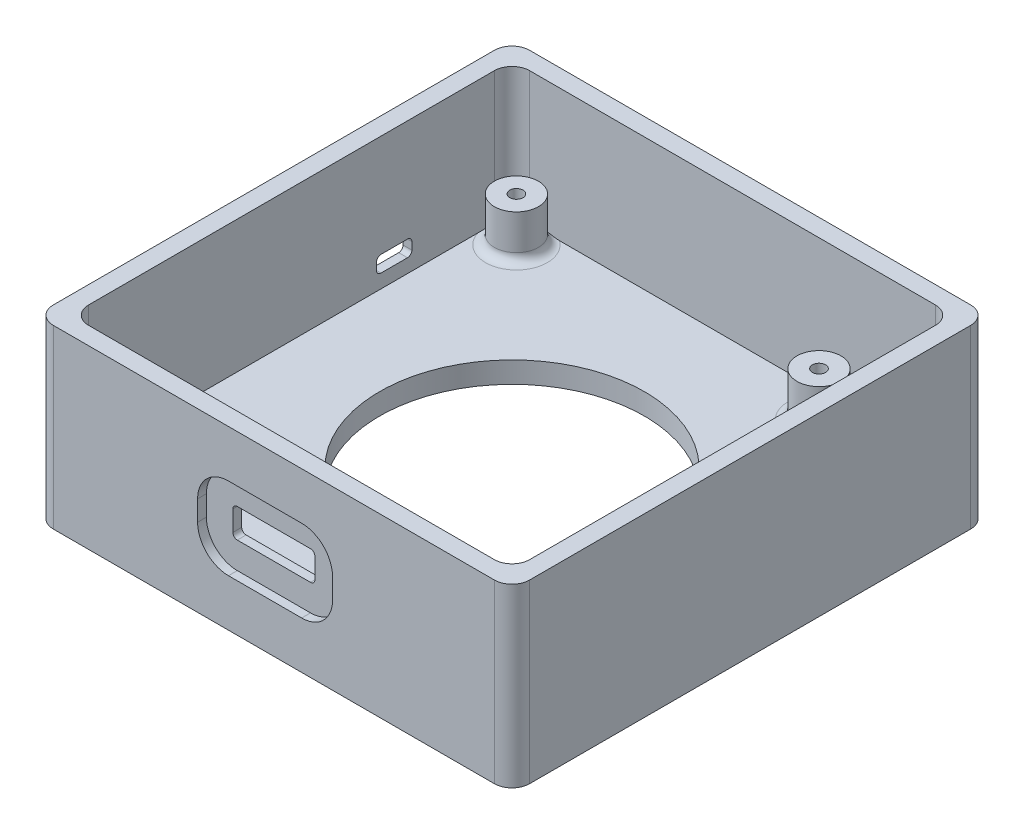
SolidWorks part; units mm, degrees
ref_plane "前视基准面" through (0, 0, 0) normal (0, 0, 1) x (1, 0, 0)
ref_plane "上视基准面" through (0, 0, 0) normal (0, 1, 0) x (1, 0, 0)
ref_plane "右视基准面" through (0, 0, 0) normal (1, 0, 0) x (0, 0, -1)
sketch "草图1" plane through (0, 0, 0) normal (0, 1, 0) x (1, 0, 0)
  line L1 (27, 27) -> (-27, 27)
  line L2 (27, 27) -> (27, -27)
  line L3 (27, -27) -> (-27, -27)
  line L4 (-27, 27) -> (-27, -27)
  line L5 (27, 27) -> (-27, -27) construction
  line L6 (27, -27) -> (-27, 27) construction
  point P1 (0, 0)
extrude "凸台-拉伸1" add sketch "草图1" along normal blind 20
sketch "草图2" plane through (0, 20, 0) normal (0, 1, 0) x (1, 0, 0)
  line L0 (-25, 25) -> (-25, -25)
  line L1 (-25, -25) -> (25, -25)
  line L2 (25, -25) -> (25, 25)
  line L3 (25, 25) -> (-25, 25)
  line L4 (-27, 27) -> (-27, -27)
  line L5 (-27, -27) -> (27, -27)
  line L6 (27, -27) -> (27, 27)
  line L7 (27, 27) -> (-27, 27)
  line L8 (-27, 27) -> (-27, -27)
  line L9 (-27, -27) -> (27, -27)
  line L10 (27, -27) -> (27, 27)
  line L11 (27, 27) -> (-27, 27)
  dimension "D1" = 0
  dimension "D2" = 2
extrude "切除-拉伸1" cut sketch "草图2" against normal blind 15 contours L2 L3 L0 L1 region at (0, 20, 0)
sketch "草图3" plane through (0, 5, 0) normal (0, 1, 0) x (1, 0, 0)
  line L0 (-25, 25) -> (-25, -25) construction
  circle A0 centre (-21.65, 22.15) radius 2.5
  circle A1 centre (-21.65, -22.15) radius 2.5
  circle A2 centre (-21.65, -22.15) radius 0.75
  circle A3 centre (-21.65, 22.15) radius 0.75
  dimension "D1" = 5
  dimension "D2" = 5
  dimension "D4" = 22.15
  dimension "D7" = 21.65
  dimension "D3" = 44.3
  dimension "D5" = 3.35
  dimension "D6" = 0
extrude "凸台-拉伸2" add sketch "草图3" along normal blind 5
fillet "圆角1" radius 1 2 edges at (-21.65, 5, 24.65) (-21.65, 5, -19.65)
ref_plane "基准面6" through (-4.5, 0, 0) normal (1, 0, 0) x (0, 0, -1)
mirror "镜向2" about plane through (-4.5, 0, 0) normal (1, 0, 0) of "圆角1", "凸台-拉伸2"
sketch "草图4" plane through (0, 0, 0) normal (0, -1, 0) x (-1, 0, 0)
  circle A0 centre (0, 0) radius 21.9
extrude "切除-拉伸2" cut sketch "草图4" against normal blind 1 contours A0
sketch "草图6" plane through (0, 1, 0) normal (0, -1, 0) x (1, 0, 0)
  circle A0 centre (0, 0) radius 18.5
extrude "切除-拉伸4" cut sketch "草图6" against normal blind 1.6
sketch "草图8" plane through (0, 2.6, 0) normal (0, -1, 0) x (1, 0, 0)
  circle A0 centre (0, 0) radius 15
extrude "切除-拉伸5" cut sketch "草图8" against normal blind 5
sketch "草图9" plane through (0, 5, 0) normal (0, 1, 0) x (1, 0, 0)
  line L1 (-3.1528, 8.925) -> (21.0647, 8.925)
  line L2 (-3.1528, 8.925) -> (-3.1528, -8.925)
  line L3 (-3.1528, -8.925) -> (21.0647, -8.925)
  line L4 (21.0647, 8.925) -> (21.0647, -8.925)
  line L5 (8.9559, -8.925) -> (8.9559, 8.925) construction
  line L6 (-3.1528, 0) -> (21.0647, 0) construction
  point P0 (8.9559, 0)
  dimension "D1" = 17.85
sketch "草图10" plane through (0, 0, 0) normal (0, -1, 0) x (1, 0, 0)
  line L0 (19.9989, -8.925) -> (-3.1528, -8.925)
  line L1 (19.9989, -8.925) -> (19.9989, 8.925)
  line L2 (-3.1528, -8.925) -> (-3.1528, 8.925)
  line L3 (-3.1528, 8.925) -> (19.9989, 8.925)
  line L4 (-27, 27) -> (-27, -27)
  line L5 (-27, -27) -> (27, -27)
  line L6 (27, -27) -> (27, 27)
  line L7 (27, 27) -> (-27, 27)
  line L8 (-27, 27) -> (-27, -27)
  line L9 (-27, -27) -> (27, -27)
  line L10 (27, -27) -> (27, 27)
  line L11 (27, 27) -> (-27, 27)
  circle A0 centre (0, 0) radius 21.9 construction
  circle A1 centre (0, 0) radius 21.9
  circle M8 centre (0, 0) radius 21.9
  dimension "D2" = 17.85
  dimension "D1" = 0
extrude "切除-拉伸6" cut sketch "草图10" against normal blind 10 contours L1 M8 | L3 L2 L0 L1 region at (8.423, 0, 0) region at (20.7622, 0, 0)
sketch "草图11" plane through (0, 0, 27) normal (0, 0, 1) x (1, 0, 0)
  line L0 (12.65, 10) -> (-0.99, 10)
  line L1 (13.4, 10) -> (11.9, 10) construction
  line L2 (-5.14, 14.65) -> (3.16, 14.65)
  line L3 (-5.14, 11.65) -> (3.16, 11.65)
  line L4 (-5.64, 11.15) -> (-5.64, 8.85)
  line L5 (-5.14, 8.35) -> (3.16, 8.35)
  line L6 (3.66, 11.15) -> (3.66, 8.85)
  line L7 (-0.99, 8.35) -> (-0.99, 11.65) construction
  line L8 (-5.64, 10) -> (3.66, 10) construction
  line L9 (6.66, 11.15) -> (6.66, 8.85)
  line L10 (-5.14, 5.35) -> (3.16, 5.35)
  line L11 (-8.64, 11.15) -> (-8.64, 8.85)
  arc A0 (-5.14, 11.65) -> (-5.64, 11.15) centre (-5.14, 11.15) ccw
  arc A1 (-5.64, 8.85) -> (-5.14, 8.35) centre (-5.14, 8.85) ccw
  arc A2 (3.16, 8.35) -> (3.66, 8.85) centre (3.16, 8.85) ccw
  arc A3 (3.16, 11.65) -> (3.66, 11.15) centre (3.16, 11.15) cw
  arc A4 (3.16, 14.65) -> (6.66, 11.15) centre (3.16, 11.15) cw
  arc A5 (3.16, 5.35) -> (6.66, 8.85) centre (3.16, 8.85) ccw
  arc A6 (-8.64, 8.85) -> (-5.14, 5.35) centre (-5.14, 8.85) ccw
  arc A7 (-5.14, 14.65) -> (-8.64, 11.15) centre (-5.14, 11.15) ccw
  point P10 (-5.64, 11.65)
  point P15 (3.66, 8.35)
  point P18 (3.66, 11.65)
  dimension "D3" = 0.5
  dimension "D1" = 9.3
  dimension "D2" = 3.3
  dimension "D4" = 3
extrude "切除-拉伸8" cut sketch "草图11" against normal blind 0.5 contours L2 A7 L11 A6 L10 A5 L9 L6 A2 L5 A1 L4 A0 L3 A3 A4 region at (6.481, 9.425, 27)
sketch "草图13" plane through (0, 0, 27) normal (0, 0, 1) x (1, 0, 0)
  line L0 (-5.14, 11.65) -> (3.16, 11.65) construction
  line L1 (-5.14, 11.65) -> (3.16, 11.65)
  line L6 (3.66, 8.85) -> (3.66, 11.15)
  line L7 (3.16, 11.65) -> (-5.14, 11.65)
  line L8 (-5.64, 11.15) -> (-5.64, 8.85)
  line L9 (-5.14, 8.35) -> (3.16, 8.35)
  line L10 (3.66, 8.85) -> (3.66, 11.15)
  line L11 (3.16, 11.65) -> (-5.14, 11.65)
  line L12 (-5.64, 11.15) -> (-5.64, 8.85)
  line L13 (-5.14, 8.35) -> (3.16, 8.35)
  arc A4 (3.66, 11.15) -> (3.16, 11.65) centre (3.16, 11.15) ccw
  arc A5 (-5.14, 11.65) -> (-5.64, 11.15) centre (-5.14, 11.15) ccw
  arc A6 (-5.64, 8.85) -> (-5.14, 8.35) centre (-5.14, 8.85) ccw
  arc A7 (3.16, 8.35) -> (3.66, 8.85) centre (3.16, 8.85) ccw
  arc A8 (3.66, 11.15) -> (3.16, 11.65) centre (3.16, 11.15) ccw
  arc A9 (-5.14, 11.65) -> (-5.64, 11.15) centre (-5.14, 11.15) ccw
  arc A10 (-5.64, 8.85) -> (-5.14, 8.35) centre (-5.14, 8.85) ccw
  arc A11 (3.16, 8.35) -> (3.66, 8.85) centre (3.16, 8.85) ccw
  line M9 (3.66, 8.85) -> (3.66, 11.15)
  arc M10 (3.66, 11.15) -> (3.16, 11.65) centre (3.16, 11.15) ccw
  line M11 (3.16, 11.65) -> (-5.14, 11.65)
  arc M12 (-5.14, 11.65) -> (-5.64, 11.15) centre (-5.14, 11.15) ccw
  line M13 (-5.64, 11.15) -> (-5.64, 8.85)
  arc M14 (-5.64, 8.85) -> (-5.14, 8.35) centre (-5.14, 8.85) ccw
  line M15 (-5.14, 8.35) -> (3.16, 8.35)
  arc M16 (3.16, 8.35) -> (3.66, 8.85) centre (3.16, 8.85) ccw
  dimension "D1" = 0
extrude "切除-拉伸9" cut sketch "草图13" against normal blind 10 contours M16 M9 M10 M11 M12 M13 M14 M15 region at (-0.99, 10, 27)
sketch "草图14" plane through (-27, 0, 0) normal (-1, 0, 0) x (0, 0, 1)
  line L7 (-10.15, 6.5578) -> (-13.15, 6.5578)
  line L8 (-9.65, 7.8878) -> (-9.65, 7.0578)
  line L9 (-13.65, 7.0578) -> (-13.65, 7.8878)
  line L10 (-13.15, 8.3878) -> (-10.15, 8.3878)
  line L15 (-13.15, 10.3878) -> (-10.15, 10.3878)
  line L16 (-7.65, 7.8878) -> (-7.65, 7.0578)
  line L17 (-10.15, 4.5578) -> (-13.15, 4.5578)
  line L18 (-15.65, 7.0578) -> (-15.65, 7.8878)
  arc A0 (-9.65, 7.0578) -> (-10.15, 6.5578) centre (-10.15, 7.0578) cw
  arc A1 (-10.15, 8.3878) -> (-9.65, 7.8878) centre (-10.15, 7.8878) cw
  arc A2 (-13.65, 7.8878) -> (-13.15, 8.3878) centre (-13.15, 7.8878) cw
  arc A3 (-13.15, 6.5578) -> (-13.65, 7.0578) centre (-13.15, 7.0578) cw
  arc A8 (-15.65, 7.8878) -> (-13.15, 10.3878) centre (-13.15, 7.8878) cw
  arc A9 (-10.15, 10.3878) -> (-7.65, 7.8878) centre (-10.15, 7.8878) cw
  arc A10 (-7.65, 7.0578) -> (-10.15, 4.5578) centre (-10.15, 7.0578) cw
  arc A11 (-13.15, 4.5578) -> (-15.65, 7.0578) centre (-13.15, 7.0578) cw
extrude "切除-拉伸10" cut sketch "草图14" against normal blind 0.5
sketch "草图15" plane through (-27, 0, 0) normal (-1, 0, 0) x (0, 0, 1)
  line L4 (-9.65, 7.0578) -> (-9.65, 7.8878)
  line L5 (-10.15, 8.3878) -> (-13.15, 8.3878)
  line L6 (-13.65, 7.8878) -> (-13.65, 7.0578)
  line L7 (-13.15, 6.5578) -> (-10.15, 6.5578)
  line L8 (-9.65, 7.0578) -> (-9.65, 7.8878)
  line L9 (-10.15, 8.3878) -> (-13.15, 8.3878)
  line L10 (-13.65, 7.8878) -> (-13.65, 7.0578)
  line L11 (-13.15, 6.5578) -> (-10.15, 6.5578)
  arc A4 (-10.15, 6.5578) -> (-9.65, 7.0578) centre (-10.15, 7.0578) ccw
  arc A5 (-9.65, 7.8878) -> (-10.15, 8.3878) centre (-10.15, 7.8878) ccw
  arc A6 (-13.15, 8.3878) -> (-13.65, 7.8878) centre (-13.15, 7.8878) ccw
  arc A7 (-13.65, 7.0578) -> (-13.15, 6.5578) centre (-13.15, 7.0578) ccw
  arc A8 (-10.15, 6.5578) -> (-9.65, 7.0578) centre (-10.15, 7.0578) ccw
  arc A9 (-9.65, 7.8878) -> (-10.15, 8.3878) centre (-10.15, 7.8878) ccw
  arc A10 (-13.15, 8.3878) -> (-13.65, 7.8878) centre (-13.15, 7.8878) ccw
  arc A11 (-13.65, 7.0578) -> (-13.15, 6.5578) centre (-13.15, 7.0578) ccw
  dimension "D1" = 0
extrude "切除-拉伸11" cut sketch "草图15" against normal blind 10
sketch "草图17" plane through (0, 0, 26.5) normal (0, 0, 1) x (1, 0, 0)
  line L4 (3.16, 14.65) -> (-5.14, 14.65)
  line L5 (-8.64, 11.15) -> (-8.64, 8.85)
  line L6 (-5.14, 5.35) -> (3.16, 5.35)
  line L7 (6.66, 8.85) -> (6.66, 11.15)
  line L8 (3.16, 14.65) -> (-5.14, 14.65)
  line L9 (-8.64, 11.15) -> (-8.64, 8.85)
  line L10 (-5.14, 5.35) -> (3.16, 5.35)
  line L11 (6.66, 8.85) -> (6.66, 11.15)
  arc A4 (-5.14, 14.65) -> (-8.64, 11.15) centre (-5.14, 11.15) ccw
  arc A5 (-8.64, 8.85) -> (-5.14, 5.35) centre (-5.14, 8.85) ccw
  arc A6 (3.16, 5.35) -> (6.66, 8.85) centre (3.16, 8.85) ccw
  arc A7 (6.66, 11.15) -> (3.16, 14.65) centre (3.16, 11.15) ccw
  arc A8 (-5.14, 14.65) -> (-8.64, 11.15) centre (-5.14, 11.15) ccw
  arc A9 (-8.64, 8.85) -> (-5.14, 5.35) centre (-5.14, 8.85) ccw
  arc A10 (3.16, 5.35) -> (6.66, 8.85) centre (3.16, 8.85) ccw
  arc A11 (6.66, 11.15) -> (3.16, 14.65) centre (3.16, 11.15) ccw
  dimension "D1" = 0
extrude "切除-拉伸12" cut sketch "草图17" against normal blind 0.5
sketch "草图18" plane through (-26.5, 0, 0) normal (-1, 0, 0) x (0, 0, 1)
  line L4 (-15.65, 7.8878) -> (-15.65, 7.0578)
  line L5 (-13.15, 4.5578) -> (-10.15, 4.5578)
  line L6 (-7.65, 7.0578) -> (-7.65, 7.8878)
  line L7 (-10.15, 10.3878) -> (-13.15, 10.3878)
  line L8 (-15.65, 7.8878) -> (-15.65, 7.0578)
  line L9 (-13.15, 4.5578) -> (-10.15, 4.5578)
  line L10 (-7.65, 7.0578) -> (-7.65, 7.8878)
  line L11 (-10.15, 10.3878) -> (-13.15, 10.3878)
  arc A4 (-13.15, 10.3878) -> (-15.65, 7.8878) centre (-13.15, 7.8878) ccw
  arc A5 (-15.65, 7.0578) -> (-13.15, 4.5578) centre (-13.15, 7.0578) ccw
  arc A6 (-10.15, 4.5578) -> (-7.65, 7.0578) centre (-10.15, 7.0578) ccw
  arc A7 (-7.65, 7.8878) -> (-10.15, 10.3878) centre (-10.15, 7.8878) ccw
  arc A8 (-13.15, 10.3878) -> (-15.65, 7.8878) centre (-13.15, 7.8878) ccw
  arc A9 (-15.65, 7.0578) -> (-13.15, 4.5578) centre (-13.15, 7.0578) ccw
  arc A10 (-10.15, 4.5578) -> (-7.65, 7.0578) centre (-10.15, 7.0578) ccw
  arc A11 (-7.65, 7.8878) -> (-10.15, 10.3878) centre (-10.15, 7.8878) ccw
  dimension "D1" = 0
extrude "切除-拉伸13" cut sketch "草图18" against normal blind 0.5
fillet "圆角5" radius 2 8 edges at (-25, 12.5, 25) (-27, 10, 27) (25, 12.5, 25) (27, 10, 27) (25, 12.5, -25) (27, 10, -27) (-25, 12.5, -25) (-27, 10, -27)
